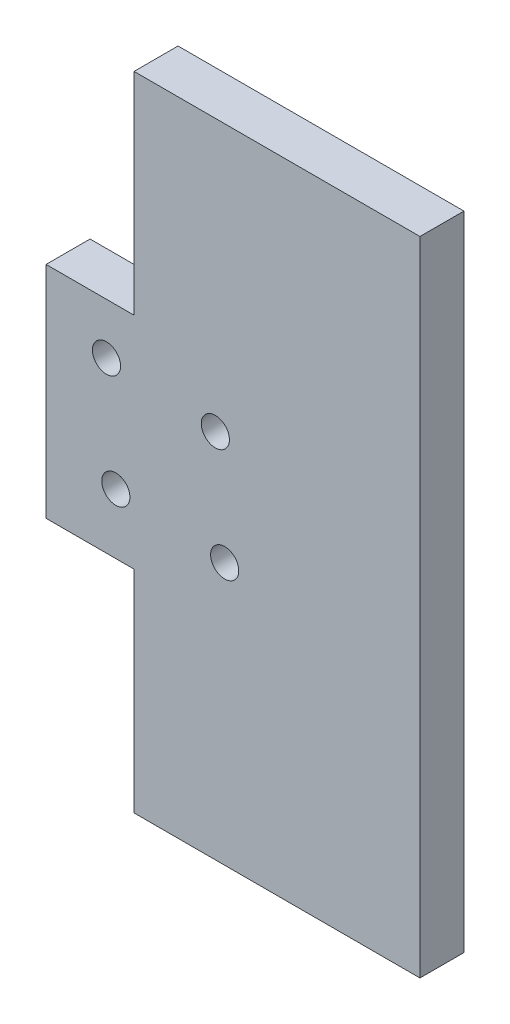
SolidWorks part; units mm, degrees
ref_plane "Front Plane" through (0, 0, 0) normal (0, 0, 1) x (1, 0, 0)
ref_plane "Top Plane" through (0, 0, 0) normal (0, 1, 0) x (1, 0, 0)
ref_plane "Right Plane" through (0, 0, 0) normal (1, 0, 0) x (0, 0, -1)
sketch "Sketch1" plane through (0, 0, 0) normal (0, 0, 1) x (1, 0, 0)
  line L1 (-16.25, 36.5) -> (16.25, 36.5)
  line L2 (-16.25, 36.5) -> (-16.25, -36.5)
  line L3 (-16.25, -36.5) -> (16.25, -36.5)
  line L4 (16.25, 36.5) -> (16.25, -36.5)
  line L5 (-16.25, 36.5) -> (16.25, -36.5) construction
  line L6 (-16.25, -36.5) -> (16.25, 36.5) construction
  point P0 (0, 0)
  dimension "D1" = 73
  dimension "D2" = 32.5
extrude "Boss-Extrude1" add sketch "Sketch1" along normal blind 5
sketch "Sketch4" plane through (-16.25, 0, 0) normal (-1, 0, 0) x (0, 0, 1)
  line L0 (5, 0) -> (0, 0) construction
  line L1 (5, 36.5) -> (5, -36.5) construction
  line L2 (0, 36.5) -> (0, -36.5) construction
  line L4 (0, -12.5) -> (5, -12.5)
  line L5 (0, -12.5) -> (0, 12.5)
  line L6 (0, 12.5) -> (5, 12.5)
  line L7 (5, -12.5) -> (5, 12.5)
  line L8 (0, -12.5) -> (5, 12.5) construction
  line L9 (0, 12.5) -> (5, -12.5) construction
  point P6 (2.5, 0)
  dimension "D1" = 25
extrude "Boss-Extrude3" add sketch "Sketch4" along normal blind 10
sketch "Sketch5" plane through (0, 0, 5) normal (0, 0, 1) x (1, 0, 0)
  line L0 (-16.25, -12.5) -> (-16.25, 12.5) construction
  line L1 (-16.25, 0) -> (-12.6641, 0) construction
  line L2 (-12.6641, 0) -> (-19.3816, 6.7175) construction
  line L3 (-12.6641, 0) -> (-7.0072, 5.6569) construction
  line L4 (-12.6641, 0) -> (-5.9466, -6.7175) construction
  line L5 (-12.6641, 0) -> (-18.3209, -5.6569) construction
  circle A0 centre (-19.3816, 6.7175) radius 1.6
  circle A1 centre (-7.0072, 5.6569) radius 1.6
  circle A2 centre (-18.3209, -5.6569) radius 1.6
  circle A3 centre (-5.9466, -6.7175) radius 1.6
extrude "Cut-Extrude1" cut sketch "Sketch5" against normal blind 25
